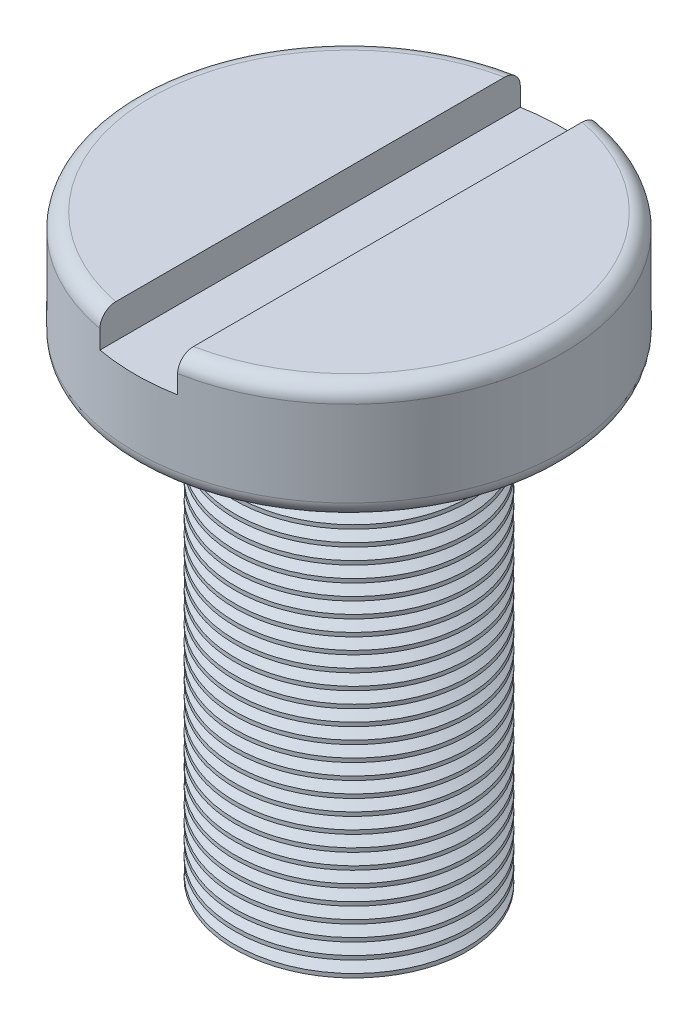
SolidWorks part; units mm, degrees
note: The reader was unsure of these and kept them because the rebuilt part matched: shared geometry of "Sketch1<3>".
ref_plane "Front" through (0, 0, 0) normal (0, 0, 1) x (1, 0, 0)
ref_plane "Top" through (0, 0, 0) normal (0, 1, 0) x (1, 0, 0)
ref_plane "Right" through (0, 0, 0) normal (1, 0, 0) x (0, 0, -1)
sketch "Sketch1" plane through (0, 0, 0) normal (0, 1, 0) x (1, 0, 0)
  circle A0 centre (0, 0) radius 2.75
  circle A1 centre (0, 0) radius 1.5
  dimension "D1" = 3
  dimension "D2" = 5.5
extrude "Boss-Extrude1" add sketch "Sketch1" along normal blind 1.5 contours A0 A1 | A1
extrude "Boss-Extrude2" add sketch "Sketch1<3>" against normal blind 6 contours A1
sketch "Sketch1<3>" plane through (0, 0, 0) normal (0, 1, 0) x (1, 0, 0) same geometry as "Sketch1"
fillet "Fillet1" radius 0.2 2 edges at (0, 1.5, 2.75) (0, 0, 2.75)
sketch "Sketch3" plane through (0, 0, 0) normal (1, 0, 0) x (0, 0, -1)
  line L0 (2.75, 1.5) -> (-2.75, 1.5) construction
  line L1 (-3.6796, 1.0626) -> (3.6796, 1.0626)
  line L2 (-3.6796, 1.0626) -> (-3.6796, 1.9374)
  line L3 (-3.6796, 1.9374) -> (3.6796, 1.9374)
  line L4 (3.6796, 1.0626) -> (3.6796, 1.9374)
  line L5 (-3.6796, 1.0626) -> (3.6796, 1.9374) construction
  line L6 (-3.6796, 1.9374) -> (3.6796, 1.0626) construction
  point P0 (0, 1.5)
extrude "Cut-Extrude1" cut sketch "Sketch3" against normal mid plane 1
sketch "Sketch4" plane through (0, 0, 0) normal (0, -1, 0) x (1, 0, 0)
  circle A0 centre (0, 0) radius 1.5
  circle A1 centre (0, 0) radius 1.5 construction
curve "Helix/Spiral1" pitch 0.2 height 6.1 turns 30.5
sketch "Sketch5" plane through (0, 0, 0) normal (0, 0, 1) x (1, 0, 0)
  line L0 (1.5, 0) -> (1.3884, -0.075)
  line L1 (1.3884, -0.075) -> (1.5, -0.15)
  line L2 (1.5, -6) -> (1.5, 0) construction
  line L3 (1.5, -0.15) -> (1.5, 0)
  line L4 (1.3884, -0.075) -> (1.5, -0.075) construction
  dimension "D1" = 0.15
sweep "Cut-Sweep1" cut profiles "Sketch5" path "Helix/Spiral1"
